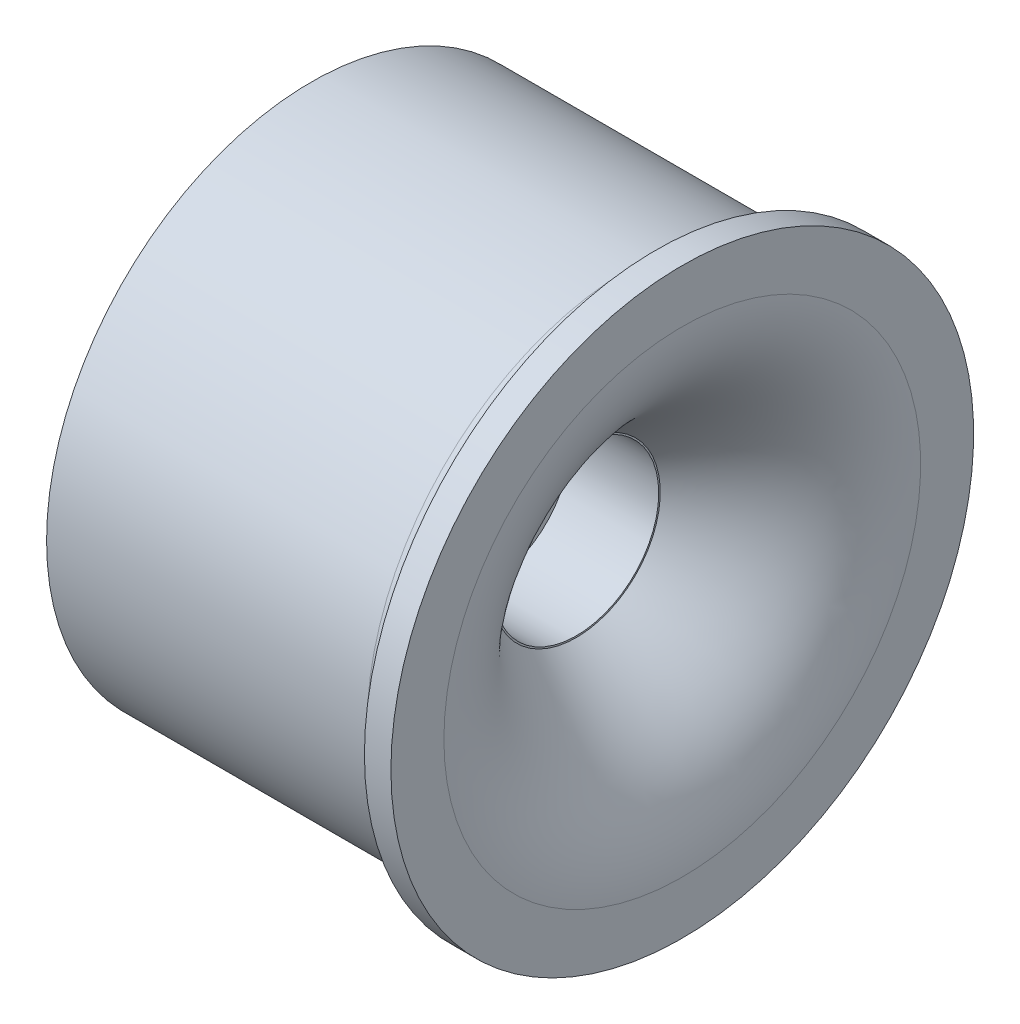
SolidWorks part; units mm, degrees
ref_plane "Front Plane" through (0, 0, 0) normal (0, 0, 1) x (1, 0, 0)
ref_plane "Top Plane" through (0, 0, 0) normal (0, 1, 0) x (1, 0, 0)
ref_plane "Right Plane" through (0, 0, 0) normal (1, 0, 0) x (0, 0, -1)
sketch "Sketch1" plane through (0, 0, 0) normal (0, 0, 1) x (1, 0, 0)
  line L0 (0, 0) -> (9.2832, 0) construction
  line L1 (0, 0) -> (0, 12.5101) construction
  line L2 (-7, 9) -> (5, 9)
  line L3 (7, 9) -> (7, 11)
  line L4 (7, 11) -> (6, 11)
  line L5 (6, 11) -> (6, 10.9)
  line L6 (5.1, 10) -> (-5.1, 10)
  line L7 (-6, 11) -> (-6, 10.9)
  line L8 (-7, 9) -> (-7, 11)
  line L9 (-7, 11) -> (-6, 11)
  line L10 (7, 7.7504) -> (7, 10.2496) construction
  line L11 (0, 3.4277) -> (0, 1)
  arc A0 (6, 10.9) -> (5.1, 10) centre (5.1, 10.9) cw
  arc A1 (-6, 10.9) -> (-5.1, 10) centre (-5.1, 10.9) ccw
  spline S0 degree 3 poles (7, 9) (7, 7.438) (5.4512, 4.5818) (0.0016, 1.0014) (0, 1) knots 0 0 0 0 0.405902 1 1 1 1
  spline S1 degree 1 poles (5, 9) (-1.3066, 2.5142) knots 0 0 1 1 construction
  spline S2 degree 3 poles (5, 9) (5, 8.8565) (4.9806, 8.5526) (4.8799, 8.0859) (4.6375, 7.5283) (3.996, 6.6902) (2.861, 5.6187) (1.4785, 4.504) (0.3776, 3.6936) (-0.3403, 3.187) (-0.6931, 2.9443) (-0.9015, 2.803) (-0.9975, 2.7385) (-1.052, 2.7022) (-1.0762, 2.6861) (-1.0898, 2.6771) (-1.0958, 2.6731) (-1.0996, 2.6706) (-1.1017, 2.6692) (-1.104, 2.6677) (-1.1061, 2.6663) (-1.1095, 2.664) (-1.1133, 2.6615) (-1.1194, 2.6574) (-1.1263, 2.6527) (-1.1365, 2.6457) (-1.1506, 2.6359) (-1.1702, 2.6222) (-1.2098, 2.5927) (-1.2456, 2.5652) (-1.2886, 2.5297) (-1.3066, 2.5142) knots 0 0 0 0 0.0625 0.125 0.25 0.375 0.5 0.625 0.75 0.8125 0.875 0.90625 0.9375 0.953125 0.96875 0.976562 0.984375 0.988281 0.992188 0.994141 0.996094 0.99707 0.998047 0.998535 0.999023 0.999268 0.999512 0.999756 0.999878 0.999939 1 1 1 1 only from (5, 9) to (0, 3.4277)
  point P12 (6, 10)
  point P16 (0, 10)
  point P18 (0, 9)
  point P22 (4.6416, 0)
  dimension "D5" = 0.9
  dimension "D1" = 7
  dimension "D2" = 2
  dimension "D3" = 1
  dimension "D4" = 1
  dimension "D6" = 10
  dimension "D7" = 1
  dimension "D8" = 5
  dimension "D9" = 2
revolve "Revolve1" add sketch "Sketch1" angle 360 about L0
sketch "Sketch2" plane through (-7, 0, 0) normal (-1, 0, 0) x (0, 0, 1)
  circle A0 centre (0, 0) radius 1 construction
  circle A1 centre (0, 0) radius 1
  circle A3 centre (0, 0) radius 5.5
  dimension "D1" = 11
extrude "Boss-Extrude1" add sketch "Sketch2" against normal blind 10
scale "Scale1" scale about centroid uniform scaling yes scale factor 0.9
sketch "Sketch3" plane through (2.7212, 0, 0) normal (1, 0, 0) x (0, 0, -1)
  circle A0 centre (0, 0) radius 2.8
  dimension "D1" = 5.6
extrude "Cut-Extrude1" cut sketch "Sketch3" against normal blind 3
sketch "Sketch4" plane through (-6.2788, 0, 0) normal (-1, 0, 0) x (0, 0, 1)
  circle A0 centre (0, 0) radius 1.42
  dimension "D1" = 2.84
extrude "Cut-Extrude2" cut sketch "Sketch4" against normal blind 7
sketch "Sketch6" plane through (0, 0, 0) normal (1, 0, 0) x (0, 0, -1)
  circle A0 centre (0, 0) radius 9 construction
  circle A1 centre (0, 0) radius 9
  circle A2 centre (0, 0) radius 12.6146
extrude "Cut-Extrude3" cut sketch "Sketch6" against normal blind 10
